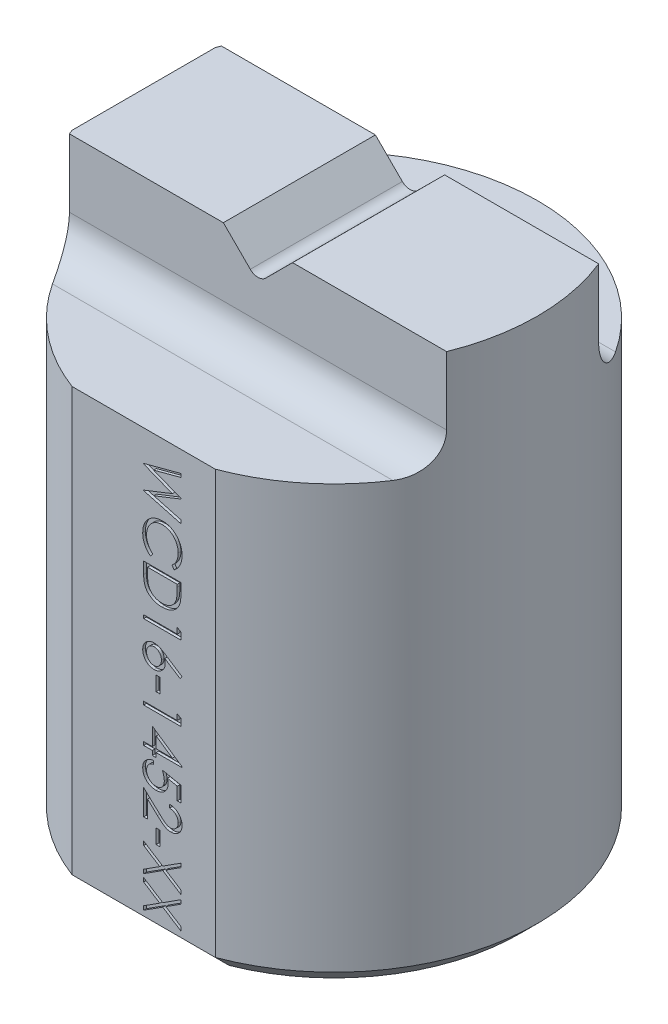
SolidWorks part; units mm, degrees
material "S7"
ref_plane "Alzado" through (0, 0, 0) normal (0, 0, 1) x (1, 0, 0)
ref_plane "Planta" through (0, 0, 0) normal (0, 1, 0) x (1, 0, 0)
ref_plane "Vista lateral" through (0, 0, 0) normal (1, 0, 0) x (0, 0, -1)
sketch "Croquis1" plane through (0, 0, 0) normal (0, 1, 0) x (1, 0, 0)
  circle A0 centre (0, 0) radius 19.0246
  dimension "D1" = 38.0492
extrude "Saliente-Extruir1" add sketch "Croquis1" along normal blind 50.8
sketch "Croquis12" plane through (0, 0, 0) normal (1, 0, 0) x (0, 0, -1)
  line L0 (7.112, 50.8) -> (19.0246, 50.8)
  line L2 (0, 50.8) -> (-7.112, 50.8) construction
  line L9 (-7.112, 50.8) -> (-19.0246, 50.8)
  line L10 (-7.112, 50.8) -> (-7.112, 44.45)
  line L11 (-10.414, 41.148) -> (-19.0246, 41.148)
  line L12 (-19.0246, 50.8) -> (-19.0246, 41.148)
  line L13 (19.0246, 50.8) -> (19.0246, 41.148)
  line L14 (0, 50.8) -> (0, 0) construction
  line L15 (19.0246, 50.8) -> (-19.0246, 50.8) construction
  line L16 (-19.0246, 50.8) -> (-19.0246, 0) construction
  line L17 (10.414, 41.148) -> (19.0246, 41.148)
  line L18 (7.112, 50.8) -> (7.112, 44.45)
  arc A0 (-7.112, 44.45) -> (-10.414, 41.148) centre (-10.414, 44.45) cw
  arc A2 (7.112, 44.45) -> (10.414, 41.148) centre (10.414, 44.45) ccw
  dimension "D3" = 3.302
  dimension "D1" = 9.652
  dimension "D2" = 14.224
extrude "Cortar-Extruir5" cut sketch "Croquis12" against normal blind 50.8 and the other way blind 50.8
sketch "Croquis14" plane through (0, 0, 0) normal (0, 0, 1) x (1, 0, 0)
  line L5 (-3.2385, 50.8) -> (-0.7172, 48.2874)
  line L10 (-17.6453, 50.8) -> (17.6453, 50.8) construction
  line L11 (0.7172, 48.2874) -> (3.2385, 50.8)
  line L12 (3.2385, 50.8) -> (-3.2385, 50.8)
  line L13 (0, 50.8) -> (0, 0) construction
  line L14 (-19.0246, 0) -> (19.0246, 0) construction
  arc A2 (-0.7172, 48.2874) -> (0.7172, 48.2874) centre (0, 49.007) ccw
  circle A3 centre (0, 50.8) radius 2.286 construction
  dimension "D1" = 6.477
  dimension "D2" = 1.016
  dimension "D3" = 4.572
extrude "Cortar-Extruir7" cut sketch "Croquis14" against normal blind 50.8 and the other way blind 50.8 contours L5 A2 L11 L12
sketch "Croquis11" plane through (0, 50.8, 0) normal (0, 1, 0) x (1, 0, 0)
  line L0 (-19.0246, 0) -> (-17.8054, 0) construction
  line L1 (0, -19.0246) -> (0, -17.8054) construction
  line L3 (-17.8054, 0) -> (-17.8054, 6.701)
  line L7 (-17.8054, 0) -> (-17.8054, -6.701)
  line L10 (-19.0246, 0) -> (19.0246, 0) construction
  line L11 (0, -17.8054) -> (-6.701, -17.8054)
  line L15 (0, -17.8054) -> (6.701, -17.8054)
  circle A0 centre (0, 0) radius 19.0246 construction
  arc A1 (-17.8054, -6.701) -> (-17.8054, 6.701) centre (0, 0) cw
  arc A2 (-6.701, -17.8054) -> (6.701, -17.8054) centre (0, 0) ccw
  arc A3 (-15.9212, -10.414) -> (15.9212, -10.414) centre (0, 0) ccw construction
  arc A4 (17.6453, -7.112) -> (17.6453, 7.112) centre (0, 0) ccw construction
  arc A5 (15.9212, 10.414) -> (-15.9212, 10.414) centre (0, 0) ccw construction
  point P24 (0, 19.0246)
  dimension "D1" = 36.83
  dimension "D2" = 36.83
extrude "Cortar-Extruir4" cut sketch "Croquis11" against normal blind 50.8
sketch "Croquis16" plane through (0, 0, 17.8054) normal (0, 0, 1) x (1, 0, 0)
  line L0 (0, 0) -> (0, 41.148) construction
  line L1 (15.9212, 41.148) -> (-15.9212, 41.148) construction
  text T0 "WCD16-1452-XX"
chamfer "Chaflán1" distance 1.5875 angle 45 4 edges at (0, 0, 17.8054) (13.4524, 0, -13.4524) (-17.8054, 0, 0) (-13.4524, 0, 13.4524)
extrude "Cortar-Extruir8" cut sketch "Croquis16" against normal blind 0.254
